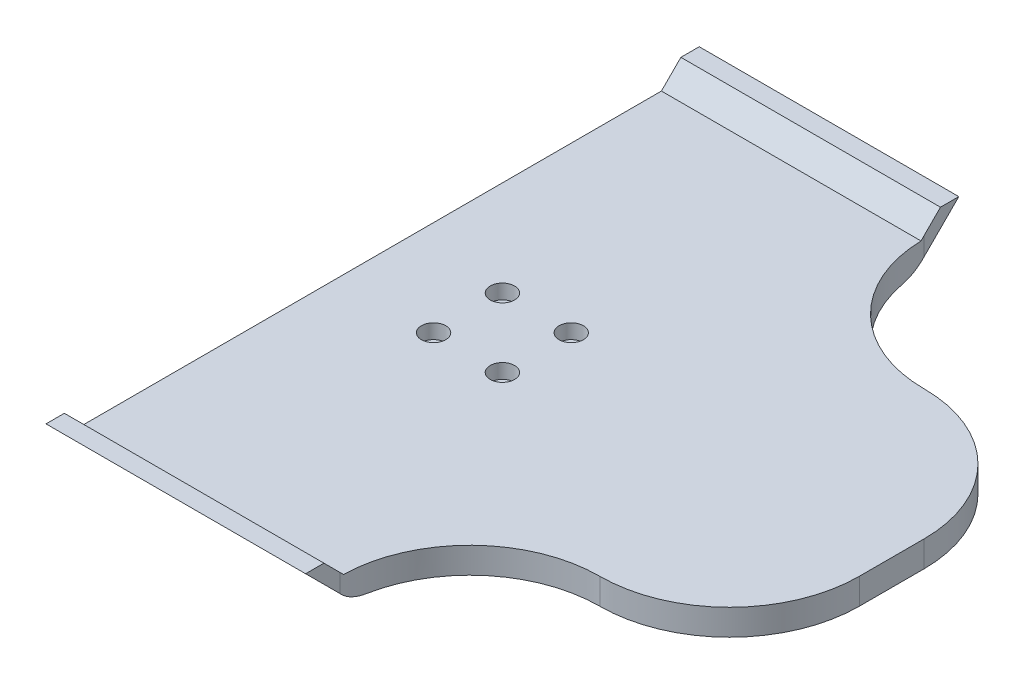
SolidWorks part; units mm, degrees
material "ABS"
ref_plane "Front Plane" through (0, 0, 0) normal (0, 0, 1) x (1, 0, 0)
ref_plane "Top Plane" through (0, 0, 0) normal (0, 1, 0) x (1, 0, 0)
ref_plane "Right Plane" through (0, 0, 0) normal (1, 0, 0) x (0, 0, -1)
sketch "Sketch2" plane through (0, 0, 0) normal (1, 0, 0) x (0, 0, -1)
  line L0 (-89, 0) -> (89, 0)
  line L1 (89, 0) -> (101.5, 12.5)
  line L2 (-89, 0) -> (-101.5, 12.5)
  line L8 (-92.3137, -8) -> (-107.1569, 6.8431)
  line L9 (-92.3137, -8) -> (92.3137, -8)
  line L10 (92.3137, -8) -> (107.1569, 6.8431)
  line L11 (-107.1569, 6.8431) -> (-101.5, 12.5)
  line L12 (101.5, 12.5) -> (107.1569, 6.8431)
  line L13 (-101.5, 12.5) -> (-114, 25) construction
  line L14 (101.5, 12.5) -> (114, 25) construction
  point P4 (0, 0)
  dimension "D2" = 135
  dimension "D3" = 135
  dimension "D1" = 228
  dimension "D4" = 25
  dimension "D5" = 8
extrude "Main" add sketch "Sketch2" along normal mid plane 80
sketch "Sketch6" plane through (0, 0, 0) normal (1, 0, 0) x (0, 0, -1)
  line L0 (-101.5, 12.5) -> (101.5, 12.5)
  line L1 (-89, 0) -> (-101.5, 12.5) construction
  line L2 (101.5, 12.5) -> (89, 0) construction
  line L3 (89, 0) -> (-89, 0) construction
  line L4 (-89, 0) -> (-101.5, 12.5)
  line L5 (89, 0) -> (-89, 0)
  line L6 (101.5, 12.5) -> (89, 0)
sketch "Sketch11" plane through (40, 0, 0) normal (1, 0, 0) x (0, 0, -1)
  line L0 (0, 0) -> (0, -8) construction
  line L1 (-92.3137, -8) -> (92.3137, -8) construction
  line L3 (50, 0) -> (-50, 0)
  line L4 (50, 0) -> (50, -8)
  line L5 (50, -8) -> (-50, -8)
  line L6 (-50, 0) -> (-50, -8)
  line L7 (50, 0) -> (-50, -8) construction
  line L8 (50, -8) -> (-50, 0) construction
  point P5 (0, -4)
  dimension "D1" = 100
extrude "Boss-Extrude1" add sketch "Sketch11" along normal blind 80
fillet "Fillet1" radius 40 4 edges at (120, -4, -50) (40, -4, -50) (40, -4, 50) (120, -4, 50)
sketch "Sketch12" plane through (0, 0, 0) normal (0, 1, 0) x (1, 0, 0)
  line L0 (0, 0) -> (-10.6066, 10.6066) construction
  line L4 (0, 0) -> (-18.1961, 0) construction
  circle A0 centre (-10.6066, 10.6066) radius 2.2
  circle A1 centre (10.6066, 10.6066) radius 2.2
  circle A2 centre (10.6066, -10.6066) radius 2.2
  circle A3 centre (-10.6066, -10.6066) radius 2.2
  point P0 (0, 0)
  point P16 (0, 0)
  dimension "D3" = 4.4
  dimension "D1" = 15
  dimension "D2" = 45
  dimension "D4" = 4
sketch "Sketch13" plane through (0, 0, 0) normal (0, 1, 0) x (1, 0, 0)
  circle A0 centre (-10.6066, 10.6066) radius 3.75
  circle A1 centre (10.6066, 10.6066) radius 3.75
  circle A2 centre (10.6066, -10.6066) radius 3.75
  circle A3 centre (-10.6066, -10.6066) radius 3.75
  point P12 (0, 0)
  dimension "D1" = 7.5
  dimension "D2" = 4
extrude "Cut-Extrude1" cut sketch "Sketch12" against normal through all
extrude "Cut-Extrude2" cut sketch "Sketch13" against normal blind 4.5
sketch "Sketch14" plane through (0, 0, 0) normal (0, 1, 0) x (1, 0, 0)
  line L1 (-40, -107.1569) -> (40, -107.1569)
  line L2 (-40, -107.1569) -> (-40, 107.1569)
  line L3 (-40, 107.1569) -> (40, 107.1569)
  line L4 (40, -107.1569) -> (40, 107.1569)
  line L5 (-40, -107.1569) -> (40, 107.1569) construction
  line L6 (-40, 107.1569) -> (40, -107.1569) construction
  point P0 (0, 0)
extrude "Cut-Extrude3" cut sketch "Sketch14" against normal blind 7 from offset 13
sketch "Sketch15" plane through (40, 0, 0) normal (1, 0, 0) x (0, 0, -1)
  line L0 (106.3137, 6) -> (92.3137, -8)
  line L1 (100.6569, 6) -> (86.6569, -8)
  line L2 (95, 6) -> (106.3137, 6) construction
  line L3 (90, -8) -> (92.3137, -8) construction
  line L4 (86.6569, -8) -> (92.3137, -8)
  line L5 (100.6569, 6) -> (106.3137, 6)
  dimension "D1" = 4
extrude "Cut-Extrude4" cut sketch "Sketch15" against normal through all from offset 1
mirror "Mirror1" about plane through (0, 0, 0) normal (0, 0, 1) of "Cut-Extrude4"
fillet "Fillet2" radius 10 2 edges at (0.07, -8, 86.6569) (0.07, -8, -86.6569)
equation "\"length\" = 215mm"
equation "\"width\" = 220mm"
equation "\"height\" = 100mm"
equation "\"skin_th\" = 8mm"
equation "\"D5@Sketch2\"=\"skin_th\""
equation "\"D1@Sketch2\"=\"width\"+8"
